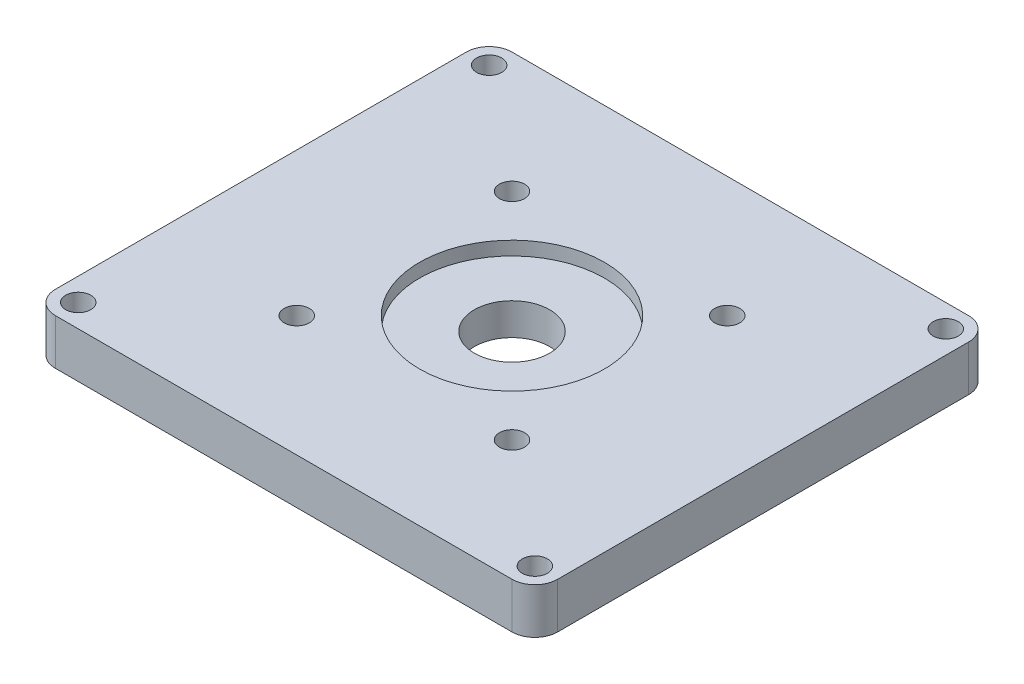
SolidWorks part; units mm, degrees
ref_plane "Front Plane" through (0, 0, 0) normal (0, 0, 1) x (1, 0, 0)
ref_plane "Top Plane" through (0, 0, 0) normal (0, 1, 0) x (1, 0, 0)
ref_plane "Right Plane" through (0, 0, 0) normal (1, 0, 0) x (0, 0, -1)
sketch "Sketch2" plane through (0, 0, 0) normal (0, 1, 0) x (1, 0, 0)
  line L1 (0, 0) -> (47.14, 0)
  line L2 (0, 0) -> (0, 47.14)
  line L3 (0, 47.14) -> (47.14, 47.14)
  line L4 (47.14, 0) -> (47.14, 47.14)
  line L5 (-26.43, 68.57) -> (73.57, 68.57)
  line L6 (-26.43, 68.57) -> (-26.43, -21.43)
  line L7 (-26.43, -21.43) -> (73.57, -21.43)
  line L8 (73.57, 68.57) -> (73.57, -21.43)
  line L9 (-31.43, 73.57) -> (78.57, 73.57)
  line L10 (-31.43, 73.57) -> (-31.43, -26.43)
  line L11 (-31.43, -26.43) -> (78.57, -26.43)
  line L12 (78.57, 73.57) -> (78.57, -26.43)
  circle A0 centre (0, 47.14) radius 2.75
  circle A1 centre (47.14, 47.14) radius 2.75
  circle A2 centre (47.14, 0) radius 2.75
  circle A3 centre (0, 0) radius 2.75
  circle A4 centre (-26.43, 68.57) radius 2.75
  circle A5 centre (73.57, 68.57) radius 2.75
  circle A6 centre (73.57, -21.43) radius 2.75
  circle A7 centre (-26.43, -21.43) radius 2.75
  dimension "D3" = 100
  dimension "D7" = 110
  dimension "D1" = 47.14
  dimension "D2" = 47.14
  dimension "D4" = 90
  dimension "D5" = 21.43
  dimension "D6" = 26.43
  dimension "D8" = 100
  dimension "D9" = 5
  dimension "D10" = 5
extrude "Boss-Extrude1" add sketch "Sketch2" along normal blind 10 contours L12 L9 L10 L11 A7 L6 A4 L5 A5 L8 A6 L7 | A7 L7 A6 L8 A5 L5 A4 L6 A3 L2 A0 L3 A1 L4 A2 L1 | A3 L1 A2 L4 A1 L3 A0 L2 region at (23.57, 0, -23.57) region at (23.57, 0, -67.2246) region at (23.57, 0, -72.0834)
sketch "Sketch3" plane through (0, 10, 0) normal (0, 1, 0) x (1, 0, 0)
  circle A0 centre (23.57, 23.57) radius 8.25
extrude "Cut-Extrude1" cut sketch "Sketch3" against normal blind 10
sketch "Sketch4" plane through (0, 10, 0) normal (0, 1, 0) x (1, 0, 0)
  circle A0 centre (23.57, 23.57) radius 20.25
extrude "Cut-Extrude2" cut sketch "Sketch4" against normal blind 3
sketch "Sketch5" plane through (0, 0, 0) normal (0, -1, 0) x (1, 0, 0)
  circle A0 centre (0, 0) radius 6.25
  circle A1 centre (47.14, 0) radius 6.25
  circle A2 centre (47.14, -47.14) radius 6.25
  circle A3 centre (0, -47.14) radius 6.25
extrude "Cut-Extrude3" cut sketch "Sketch5" against normal blind 5.5
fillet "Fillet1" radius 5 4 edges at (-31.43, 5, -73.57) (78.57, 5, -73.57) (78.57, 5, 26.43) (-31.43, 5, 26.43)
